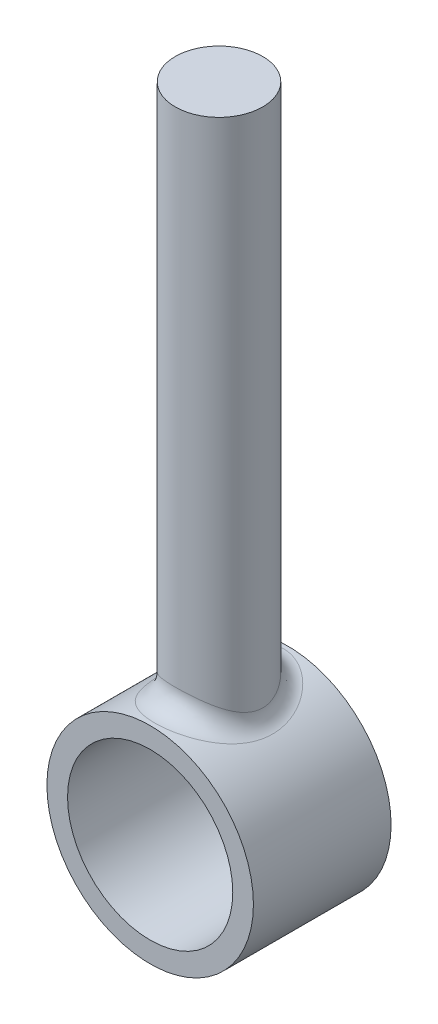
SolidWorks part; units mm, degrees
material "Alloy Steel"
ref_plane "Front Plane" through (0, 0, 0) normal (0, 0, 1) x (1, 0, 0)
ref_plane "Top Plane" through (0, 0, 0) normal (0, 1, 0) x (1, 0, 0)
ref_plane "Right Plane" through (0, 0, 0) normal (1, 0, 0) x (0, 0, -1)
sketch "Sketch1" plane through (0, 0, 0) normal (0, 1, 0) x (1, 0, 0)
  circle A0 centre (0, 0) radius 3.175
  dimension "D1" = 6.35
sketch "Sketch2" plane through (0, 0, 0) normal (0, 1, 0) x (-1, 0, 0)
  circle A0 centre (0, 0) radius 3.175
  dimension "D1" = 6.35
sketch "Sketch4" plane through (0, 0, 0) normal (0, 0, -1) x (-1, 0, 0)
  line L0 (0, 0) -> (0, -25.978) construction
  line L2 (0, -18.478) -> (3.25, -18.478) construction
  circle A0 centre (0, -25.978) radius 7.5
  dimension "D1" = 15
  dimension "D2" = 18.478
extrude "Boss-Extrude4" add sketch "Sketch4" against normal mid plane 10 contours A0
sketch "Sketch5" plane through (0, 0, -5) normal (0, 0, 1) x (1, 0, 0)
  circle A0 centre (0, -25.978) radius 6
  circle A1 centre (0, -25.978) radius 7.5 construction
  dimension "D1" = 12
extrude "Cut-Extrude1" cut sketch "Sketch5" along normal through all
hole_wizard "M3x0.5 Tapped Hole1" [suppressed] positions "Sketch8" profile "Sketch7" tap size "M3x0.5" standard "ANSI Metric"
sketch "Sketch8" plane through (0, 21, 0) normal (0, 1, 0) x (1, 0, 0)
  point P0 (0, 0)
sketch "Sketch7" plane through (0, 21, 0) normal (1, 0, 0) x (0, 0, 1)
  line L0 (0, 0) -> (0, 8.2511)
  line L1 (0, 8.2511) -> (1.25, 7.5)
  line L2 (1.25, 7.5) -> (1.25, 0)
  line L5 (1.25, 0) -> (0, 0)
  line L10 (0, 8.2511) -> (-1.25, 7.5) construction
  line L11 (0, -6.35) -> (0, 107.95) construction
  dimension "Tap Drill Dia." = 2.5
  dimension "Tap Drill Depth" = 7.5
  dimension "Drill Angle" = 118
cosmetic thread "Hole Thread1" [suppressed] parameters "D1"=6, "D2"=3
ref_plane "Plane1" through (0, 0, 0) normal (0, 0, 1) x (1, 0, 0)
extrude "Boss-Extrude5" add sketch "Sketch1" against normal up to surface (18.478 mm away) up to face at (-7.5, -25.978, 5)
sketch "Sketch11" plane through (0, 0, 5) normal (0, 0, 1) x (1, 0, 0)
  line L0 (0, 19.522) -> (6, 19.522) construction
  line L1 (0, 19.522) -> (0, 0) construction
  circle A0 centre (0, -25.978) radius 6 construction
  circle A1 centre (0, -25.978) radius 6 construction
  dimension "D1" = 45.5
extrude "Boss-Extrude6" add sketch "Sketch2" along normal up to vertex (19.522 mm away) up to point (0, 19.522, 5)
fillet "Fillet1" radius 1.5 1 edges at (-0.4299, -18.4903, -3.1458)
